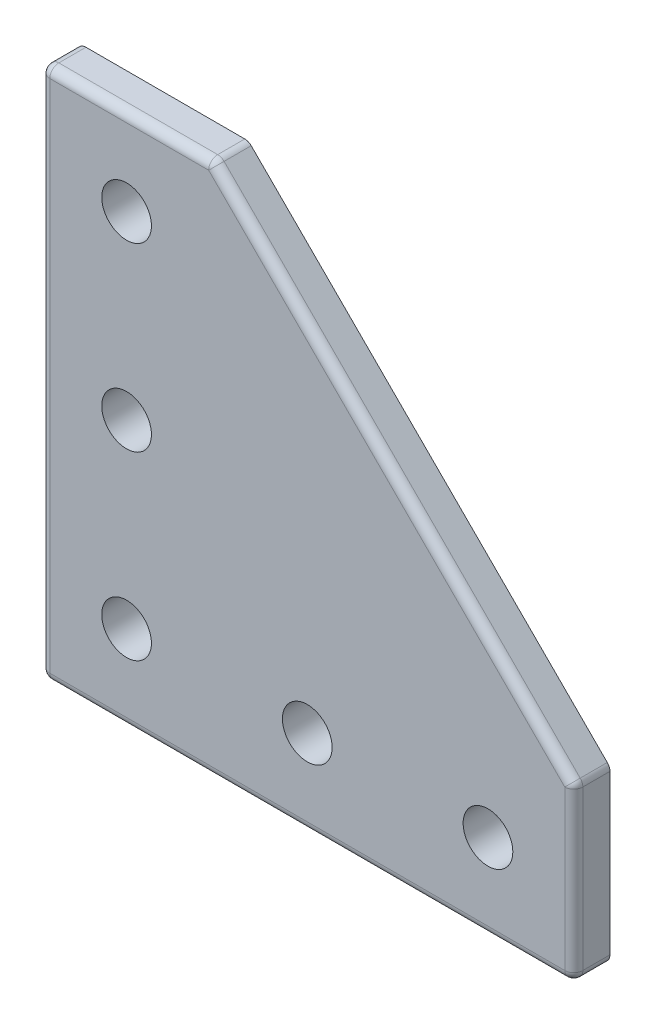
SolidWorks part; units mm, degrees
ref_plane "Front Plane" through (0, 0, 0) normal (0, 0, 1) x (1, 0, 0)
ref_plane "Top Plane" through (0, 0, 0) normal (0, 1, 0) x (1, 0, 0)
ref_plane "Right Plane" through (0, 0, 0) normal (1, 0, 0) x (0, 0, -1)
sketch "Sketch1" plane through (0, 0, 0) normal (0, 0, 1) x (1, 0, 0)
  line L0 (0, 0) -> (0, 59)
  line L1 (9.5, 9.5) -> (29.5, 9.5) construction
  line L2 (29.5, 9.5) -> (49.5, 9.5) construction
  line L3 (9.5, 9.5) -> (9.5, 29.5) construction
  line L4 (19, 59) -> (0, 59)
  line L5 (59, 0) -> (0, 0)
  line L6 (9.5, 29.5) -> (9.5, 49.5) construction
  line L7 (59, 19) -> (59, 0)
  line L8 (19, 59) -> (59, 19)
  line L9 (59, 9.5) -> (49.5, 9.5) construction
  line L10 (9.5, 59) -> (9.5, 49.5) construction
  circle A0 centre (9.5, 9.5) radius 2.75
  circle A1 centre (29.5, 9.5) radius 2.75
  circle A2 centre (49.5, 9.5) radius 2.75
  circle A3 centre (9.5, 29.5) radius 2.75
  circle A4 centre (9.5, 49.5) radius 2.75
  dimension "D1" = 20
  dimension "E" = 5.5
  dimension "D2" = 9.5
  dimension "C" = 59
  dimension "D3" = 20
  dimension "B" = 59
  dimension "D4" = 9.5
extrude "Boss-Extrude1" add sketch "Sketch1" along normal mid plane 4
fillet "Fillet1" radius 1 10 edges at (0, 0, 0) (0, 29.5, 2) (29.5, 0, 2) (59, 9.5, 2) (59, 0, 0) (9.5, 59, 2) (0, 59, 0) (39, 39, 2) (59, 19, 0) (19, 59, 0)
ref_axis "Axis1" through (9.5, 49.5, 2) along (0, 0, -1)
ref_axis "Axis2" through (9.5, 9.5, 2) along (0, 0, -1)
ref_axis "Axis3" through (49.5, 9.5, 2) along (0, 0, -1)
ref_plane "Plane1" through (9.5, 0, 0) normal (-1, 0, 0) x (0, 0, 1)
ref_plane "Plane2" through (0, 9.5, 0) normal (0, -1, 0) x (-1, 0, 0)
